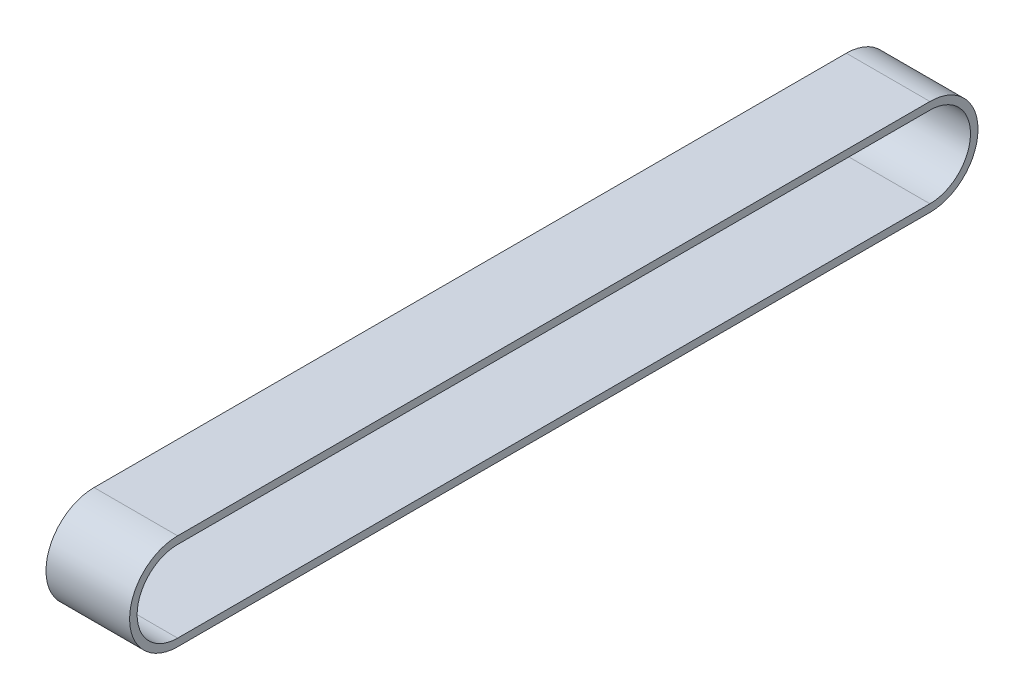
SolidWorks part; units mm, degrees
material "PUR"
ref_plane "Front" through (0, 0, 0) normal (0, 0, 1) x (1, 0, 0)
ref_plane "Top" through (0, 0, 0) normal (0, 1, 0) x (1, 0, 0)
ref_plane "Right" through (0, 0, 0) normal (1, 0, 0) x (0, 0, -1)
sketch "Sketch1" plane through (0, 0, 0) normal (1, 0, 0) x (0, 0, -1)
  line L0 (-114.3, 0) -> (114.3, 0) construction
  line L1 (-114.3, 14.605) -> (114.3, 14.605)
  line L2 (-114.3, -14.605) -> (114.3, -14.605)
  line L3 (-114.3, 0) -> (114.3, 0) construction
  line L4 (-114.3, 12.319) -> (114.3, 12.319)
  line L5 (-114.3, -12.319) -> (114.3, -12.319)
  arc A0 (-114.3, 14.605) -> (-114.3, -14.605) centre (-114.3, 0) ccw
  arc A1 (114.3, -14.605) -> (114.3, 14.605) centre (114.3, 0) ccw
  arc A2 (-114.3, 12.319) -> (-114.3, -12.319) centre (-114.3, 0) ccw
  arc A3 (114.3, -12.319) -> (114.3, 12.319) centre (114.3, 0) ccw
  point P2 (0, 0)
  point P9 (0, 0)
  dimension "D2" = 24.638
  dimension "D1" = 2.286
  dimension "D3" = 228.6
extrude "Boss-Extrude1" add sketch "Sketch1" along normal mid plane 25.4
